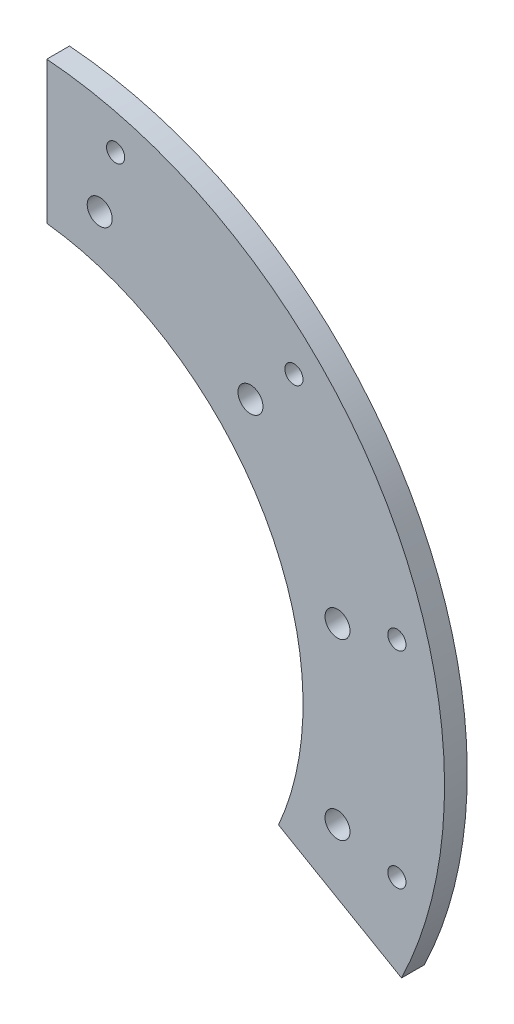
SolidWorks part; units mm, degrees
material "Teck"
ref_plane "Plan de face" through (0, 0, 0) normal (0, 0, 1) x (1, 0, 0)
ref_plane "Plan de dessus" through (0, 0, 0) normal (0, 1, 0) x (1, 0, 0)
ref_plane "Plan de droite" through (0, 0, 0) normal (1, 0, 0) x (0, 0, -1)
sketch "Esquisse1" plane through (0, 0, 0) normal (0, 0, 1) x (1, 0, 0)
  line L0 (6, 75.7628) -> (6, 50.7465)
  line L1 (68.4339, -33.0575) -> (46.7826, -20.5572)
  line L2 (0, 73.61) -> (0, 0) construction
  line L3 (0, 0) -> (63.7481, -36.805) construction
  arc A0 (6, 50.7465) -> (46.7826, -20.5572) centre (0, 0) cw
  arc A2 (6, 75.7628) -> (68.4339, -33.0575) centre (0, 0) cw
  circle A3 centre (0, 0) radius 73.61 construction
  point P1 (0, 0)
  point P4 (0, 0)
  dimension "D4" = 76
  dimension "D5" = 51.1
  dimension "D1" = 120
  dimension "D2" = 6
  dimension "D3" = 6
extrude "Boss.-Extru.1" add sketch "Esquisse1" along normal blind 4 contours L0 A0 L1 A2
sketch "Sketch2" plane through (0, 0, 4) normal (0, 0, 1) x (1, 0, 0)
  line L0 (0, 0) -> (0, 96.9743) construction
  line L1 (0, 0) -> (18.1173, 67.6148) construction
  line L2 (18.1173, 67.6148) -> (29.3318, 109.4676) construction
  circle A0 centre (18.1173, 67.6148) radius 1.6
  circle A1 centre (15.3169, 57.1635) radius 2.2
  point P7 (35.0097, 96.9743)
  dimension "D2" = 3.2
  dimension "D4" = 4.4
  dimension "D1" = 70
  dimension "D3" = 59.18
  dimension "D5" = 15
extrude "Cut-Extrude1" cut sketch "Sketch2" against normal through all
ref_axis "Axis1" through (0, 0, -0.2) along (0, 0, 1)
pattern_circular "CirPattern1" count 12 over 360 about axis through (0, 0, -0.2) along (0, 0, 1) of "Cut-Extrude1" reverse direction yes
